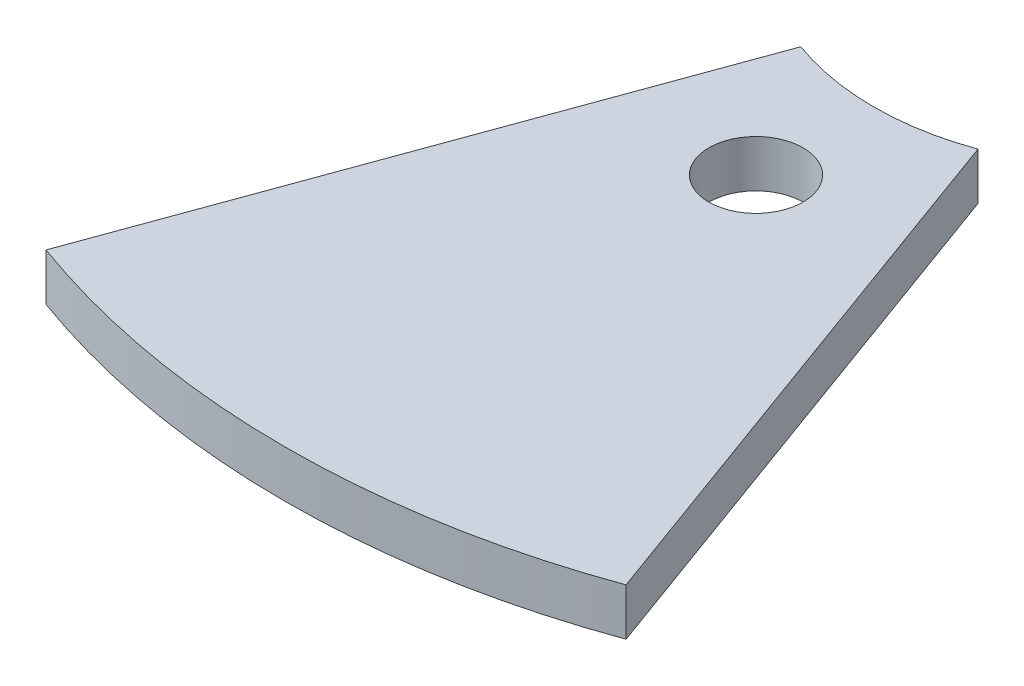
SolidWorks part; units mm, degrees
ref_plane "Front Plane" through (0, 0, 0) normal (0, 0, 1) x (1, 0, 0)
ref_plane "Top Plane" through (0, 0, 0) normal (0, 1, 0) x (1, 0, 0)
ref_plane "Right Plane" through (0, 0, 0) normal (1, 0, 0) x (0, 0, -1)
sketch "Sketch1" plane through (0, 0, 0) normal (0, 1, 0) x (1, 0, 0)
  line L0 (0, 50.8) -> (-39.0929, -56.6069)
  line L1 (0, 50.8) -> (0, 0) construction
  line L2 (0, 50.8) -> (39.0929, -56.6069)
  circle A0 centre (0, 0) radius 6.35
  circle A1 centre (0, 50.8) radius 114.3
  circle A2 centre (0, 50.8) radius 34.925
  point P3 (0, 50.8)
  dimension "D1" = 20
  dimension "D3" = 69.85
  dimension "D4" = 228.6
  dimension "D2" = 50.8
extrude "Boss-Extrude1" add sketch "Sketch1" along normal blind 6.35 contours A2 L0 A1 L2 A0 region at (0, 0, 30.1242)
ref_point "Point1"
